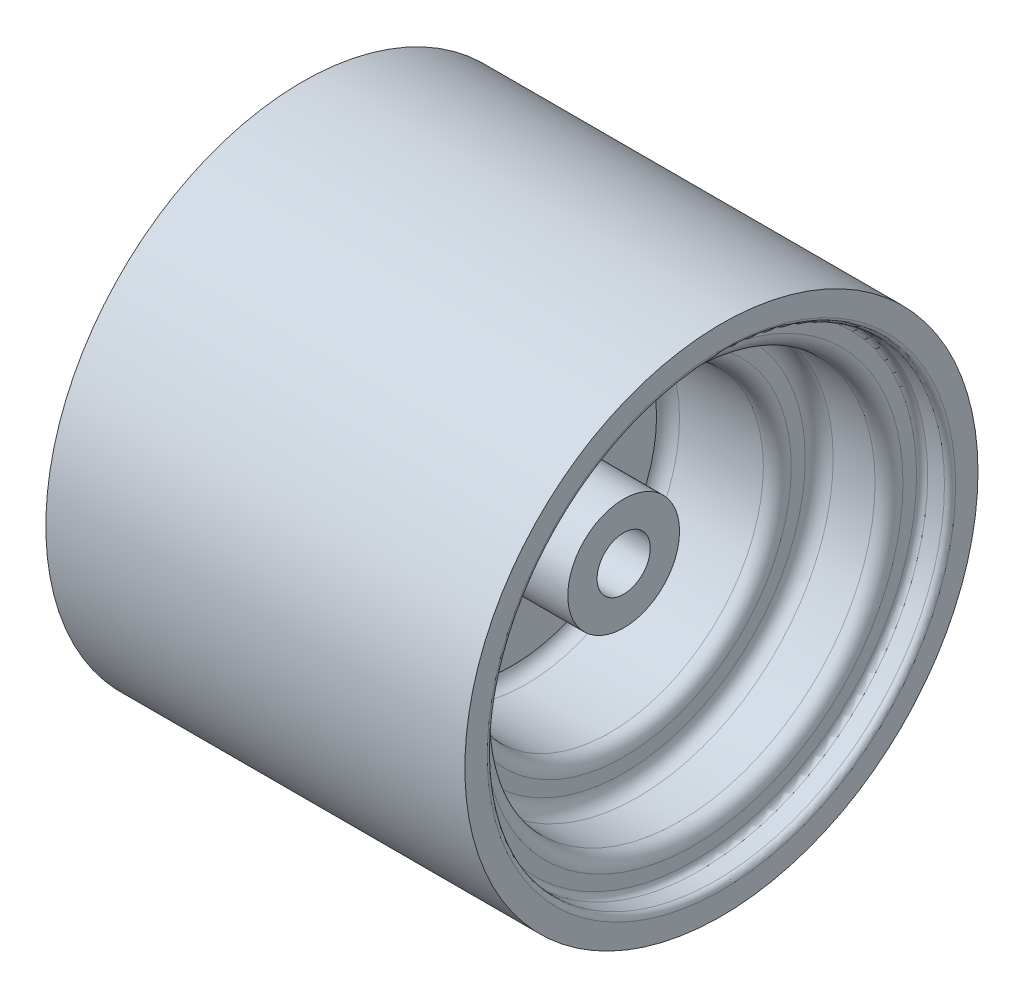
SolidWorks part; units mm, degrees
material "PS Medium/High Flow"
ref_plane "Front Plane" through (0, 0, 0) normal (0, 0, 1) x (1, 0, 0)
ref_plane "Top Plane" through (0, 0, 0) normal (0, 1, 0) x (1, 0, 0)
ref_plane "Right Plane" through (0, 0, 0) normal (1, 0, 0) x (0, 0, -1)
sketch "Sketch1" plane through (0, 0, 0) normal (1, 0, 0) x (0, 0, -1)
  circle A0 centre (0, 0) radius 91.845
extrude "Boss-Extrude1" add sketch "Sketch1" along normal blind 150.24
sketch "Sketch2" plane through (150.24, 0, 0) normal (1, 0, 0) x (0, 0, -1)
  circle A0 centre (0, 0) radius 81.845
extrude "Cut-Extrude1" cut sketch "Sketch2" against normal blind 10
sketch "Sketch3" plane through (140.24, 0, 0) normal (1, 0, 0) x (0, 0, -1)
  circle A0 centre (0, 0) radius 70
extrude "Cut-Extrude2" cut sketch "Sketch3" against normal blind 25
sketch "Sketch4" plane through (115.24, 0, 0) normal (1, 0, 0) x (0, 0, -1)
  circle A0 centre (0, 0) radius 55
extrude "Cut-Extrude3" cut sketch "Sketch4" against normal blind 40
sketch "Sketch5" plane through (75.24, 0, 0) normal (1, 0, 0) x (0, 0, -1)
  circle A0 centre (0, 0) radius 20
extrude "Boss-Extrude3" add sketch "Sketch5" along normal blind 40
ref_plane "Plane1" through (75.24, 0, 0) normal (1, 0, 0) x (0, 0, -1)
sketch "Sketch6" plane through (0, 0, 0) normal (-1, 0, 0) x (0, 0, 1)
  circle A0 centre (0, 0) radius 91.845
extrude "Cut-Extrude4" cut sketch "Sketch6" against normal blind 75
fillet "Fillet1" radius 2 1 edges at (150.24, 0, -81.845)
fillet "Fillet2" radius 5 1 edges at (140.24, 0, -70)
fillet "Fillet3" radius 5 1 edges at (115.24, 0, -70)
fillet "Fillet4" radius 2 1 edges at (140.24, 0, -81.845)
fillet "Fillet5" radius 5 1 edges at (115.24, 0, -55)
fillet "Fillet6" radius 5 1 edges at (75.24, 0, -55)
fillet "Fillet7" radius 2 1 edges at (75.24, 0, -20)
sketch "Sketch7" plane through (115.24, 0, 0) normal (1, 0, 0) x (0, 0, -1)
  circle A0 centre (0, 0) radius 9.525
extrude "Cut-Extrude5" cut sketch "Sketch7" against normal blind 75
mirror "Mirror9" about plane through (75.24, 0, 0) normal (1, 0, 0) of bodies 115
ref_axis "Axis1" through (35.24, 0, 0) along (1, 0, 0)
